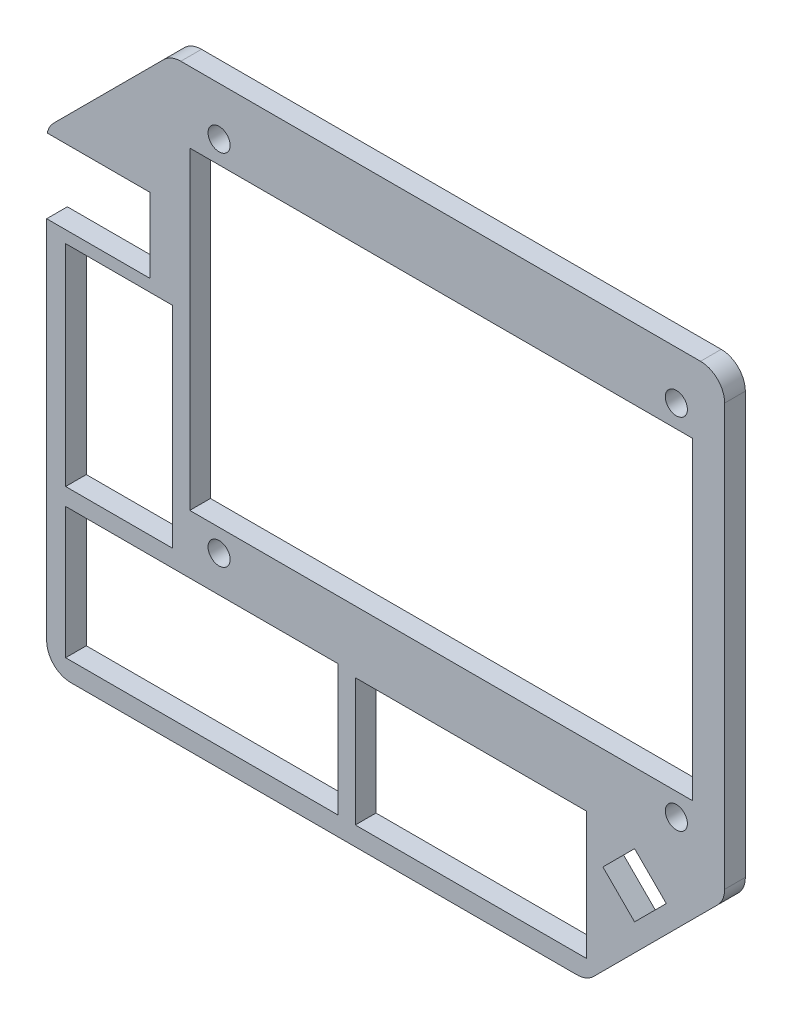
SolidWorks part; units mm, degrees
material "Acrylic (Medium-high impact)"
ref_plane "Front Plane" through (0, 0, 0) normal (0, 0, 1) x (1, 0, 0)
ref_plane "Top Plane" through (0, 0, 0) normal (0, 1, 0) x (1, 0, 0)
ref_plane "Right Plane" through (0, 0, 0) normal (1, 0, 0) x (0, 0, -1)
sketch "Sketch1" plane through (0, 0, 0) normal (0, 0, 1) x (1, 0, 0)
  line L0 (0, 66) -> (-18, 48)
  line L1 (0, 0) -> (80.3, 0)
  line L2 (0, 0) -> (0, 66)
  line L3 (0, 66) -> (80.3, 66)
  line L4 (80.3, 0) -> (80.3, 66)
  line L5 (-18, 48) -> (-18, -20)
  line L6 (-18, -20) -> (60.3, -20)
  line L7 (60.3, -20) -> (80.3, 0)
  dimension "D1" = 80.3
  dimension "D2" = 66
  dimension "D3" = 20
  dimension "D4" = 18
  dimension "D5" = 45
  dimension "D6" = 45
extrude "Boss-Extrude1" add sketch "Sketch1" along normal blind 3 contours L6 L7 L1 L2 L0 L5 | L1 L4 L3 L2 region at (-1.3061, 33, 0) region at (40.15, 33, 0)
fillet "Fillet1" radius 3.5 6 edges at (80.3, 0, 1.5) (60.3, -20, 1.5) (-18, -20, 1.5) (-18, 48, 1.5) (80.3, 66, 1.5) (0, 66, 1.5)
sketch "Sketch2" plane through (0, 0, 3) normal (0, 0, 1) x (1, 0, 0)
  line L1 (3, 10.5) -> (75.4, 10.5)
  line L2 (3, 10.5) -> (3, 55.5)
  line L3 (3, 55.5) -> (75.4, 55.5)
  line L4 (75.4, 10.5) -> (75.4, 55.5)
  line L6 (80.3, 1.4497) -> (80.3, 62.5) construction
  line L7 (1.4497, 66) -> (76.8, 66) construction
  dimension "D1" = 4.9
  dimension "D2" = 3
  dimension "D3" = 10.5
  dimension "D4" = 45
extrude "Cut-Extrude1" cut sketch "Sketch2" against normal through all contours L1 L4 L3 L2 region at (39.2, 33, 3)
sketch "Sketch3" plane through (0, 0, 3) normal (0, 0, 1) x (1, 0, 0)
  line L1 (27, -17) -> (60, -17)
  line L2 (27, -17) -> (27, 1)
  line L3 (27, 1) -> (60, 1)
  line L4 (60, -17) -> (60, 1)
  line L5 (-15, -17) -> (24, -17)
  line L6 (-15, -17) -> (-15, 1.5)
  line L7 (-15, 1.5) -> (24, 1.5)
  line L8 (24, -17) -> (24, 1.5)
  line L9 (0, 4.5) -> (-15, 4.5)
  line L10 (0, 4.5) -> (0, 34.5)
  line L11 (0, 34.5) -> (-15, 34.5)
  line L12 (-15, 4.5) -> (-15, 34.5)
  line L13 (-18, 47.3) -> (-3, 47.3)
  line L14 (-18, 47.3) -> (-18, 36.5)
  line L15 (-18, 36.5) -> (-3, 36.5)
  line L16 (-3, 47.3) -> (-3, 36.5)
  line L17 (-14.5, -20) -> (58.8503, -20) construction
  line L18 (-18, 46.5503) -> (-18, -16.5) construction
  line L21 (67.2426, -8.8147) -> (71.4853, -4.5721)
  line L22 (71.4853, -4.5721) -> (67.2426, -0.3294)
  line L23 (67.2426, -0.3294) -> (63, -4.5721)
  line L24 (63, -4.5721) -> (67.2426, -8.8147)
  line L25 (61.3251, -18.9749) -> (79.2749, -1.0251) construction
  arc M12 (-16.9749, 49.0251) -> (-18, 46.5503) centre (-14.5, 46.5503) ccw
  line M13 (-18, 46.5503) -> (-18, -16.5)
  dimension "D1" = 18
  dimension "D2" = 18.5
  dimension "D3" = 39
  dimension "D4" = 33
  dimension "D5" = 15
  dimension "D6" = 30
  dimension "D7" = 10.8
  dimension "D8" = 15
  dimension "D9" = 3
  dimension "D10" = 3
  dimension "D11" = 3
  dimension "D12" = 3
  dimension "D13" = 3
  dimension "D14" = 3
  dimension "D15" = 2
  dimension "D16" = 6
  dimension "D17" = 6
  dimension "D18" = 6
  dimension "D19" = 3
  dimension "D20" = 3
extrude "Cut-Extrude2" cut sketch "Sketch3" against normal through all contours L16 L13 L15 M12 M13 | L12 L9 L10 L11 | L1 L4 L3 L2 | L5 L8 L7 L6 | L23 L24 L21 L22 region at (43.5, -8, 3) region at (4.5, -7.75, 3) region at (-7.5, 19.5, 3) region at (-10.4991, 41.8993, 3) region at (67.2426, -4.5721, 3)
hole_wizard "Ø3.2 (3.2) Diameter Hole1" positions "Sketch5" profile "Sketch6" hole size "Ø3.2" standard "ANSI Metric" end condition through all
sketch "Sketch5" plane through (0, 0, 3) normal (0, 0, 1) x (1, 0, 0)
  line L5 (80.3, 1.4497) -> (80.3, 62.5) construction
  line L7 (1.4497, 66) -> (76.8, 66) construction
  point P0 (7, 59)
  point P2 (73.3, 59)
  point P4 (73.3, 7)
  point P6 (7, 7)
  dimension "D1" = 7
  dimension "D2" = 7
  dimension "D3" = 66.3
  dimension "D4" = 52
sketch "Sketch6" plane through (7, 59, 3) normal (1, 0, 0) x (0, -1, 0)
  line L0 (0, 0) -> (0, 3)
  line L1 (0, 3) -> (1.6, 3)
  line L2 (1.6, 3) -> (1.6, 0)
  line L5 (1.6, 0) -> (0, 0)
  line L11 (0, -6.35) -> (0, 107.95) construction
  dimension "Thru Hole Dia." = 3.2
  dimension "Thru Hole Depth" = 3
sketch "Sketch9" plane through (0, 0, 3) normal (0, 0, 1) x (1, 0, 0)
  line L8 (2.75, 55.75) -> (2.75, 10.25)
  line L9 (2.75, 10.25) -> (75.65, 10.25)
  line L10 (75.65, 10.25) -> (75.65, 55.75)
  line L11 (75.65, 55.75) -> (2.75, 55.75)
  line L12 (2.75, 55.75) -> (2.75, 10.25)
  line L13 (2.75, 10.25) -> (75.65, 10.25)
  line L14 (75.65, 10.25) -> (75.65, 55.75)
  line L15 (75.65, 55.75) -> (2.75, 55.75)
  line L20 (26.75, 1.25) -> (26.75, -17.25)
  line L21 (26.75, -17.25) -> (60.25, -17.25)
  line L22 (60.25, -17.25) -> (60.25, 1.25)
  line L23 (60.25, 1.25) -> (26.75, 1.25)
  line L24 (26.75, 1.25) -> (26.75, -17.25)
  line L25 (26.75, -17.25) -> (60.25, -17.25)
  line L26 (60.25, -17.25) -> (60.25, 1.25)
  line L27 (60.25, 1.25) -> (26.75, 1.25)
  line L32 (67.2426, -9.1683) -> (71.8388, -4.5721)
  line L33 (62.6464, -4.5721) -> (67.2426, -9.1683)
  line L34 (67.2426, 0.0241) -> (62.6464, -4.5721)
  line L35 (71.8388, -4.5721) -> (67.2426, 0.0241)
  line L36 (67.2426, -9.1683) -> (71.8388, -4.5721)
  line L37 (62.6464, -4.5721) -> (67.2426, -9.1683)
  line L38 (67.2426, 0.0241) -> (62.6464, -4.5721)
  line L39 (71.8388, -4.5721) -> (67.2426, 0.0241)
  line L44 (-15.25, 1.75) -> (-15.25, -17.25)
  line L45 (-15.25, -17.25) -> (24.25, -17.25)
  line L46 (24.25, -17.25) -> (24.25, 1.75)
  line L47 (24.25, 1.75) -> (-15.25, 1.75)
  line L48 (-15.25, 1.75) -> (-15.25, -17.25)
  line L49 (-15.25, -17.25) -> (24.25, -17.25)
  line L50 (24.25, -17.25) -> (24.25, 1.75)
  line L51 (24.25, 1.75) -> (-15.25, 1.75)
  line L56 (0.25, 34.75) -> (-15.25, 34.75)
  line L57 (0.25, 4.25) -> (0.25, 34.75)
  line L58 (-15.25, 4.25) -> (0.25, 4.25)
  line L59 (-15.25, 34.75) -> (-15.25, 4.25)
  line L60 (0.25, 34.75) -> (-15.25, 34.75)
  line L61 (0.25, 4.25) -> (0.25, 34.75)
  line L62 (-15.25, 4.25) -> (0.25, 4.25)
  line L63 (-15.25, 34.75) -> (-15.25, 4.25)
  dimension "D1" = 0.25
  dimension "D2" = 0.25
  dimension "D3" = 0.25
  dimension "D4" = 0.25
  dimension "D5" = 0.25
extrude "Cut-Extrude3" cut sketch "Sketch9" against normal through all
